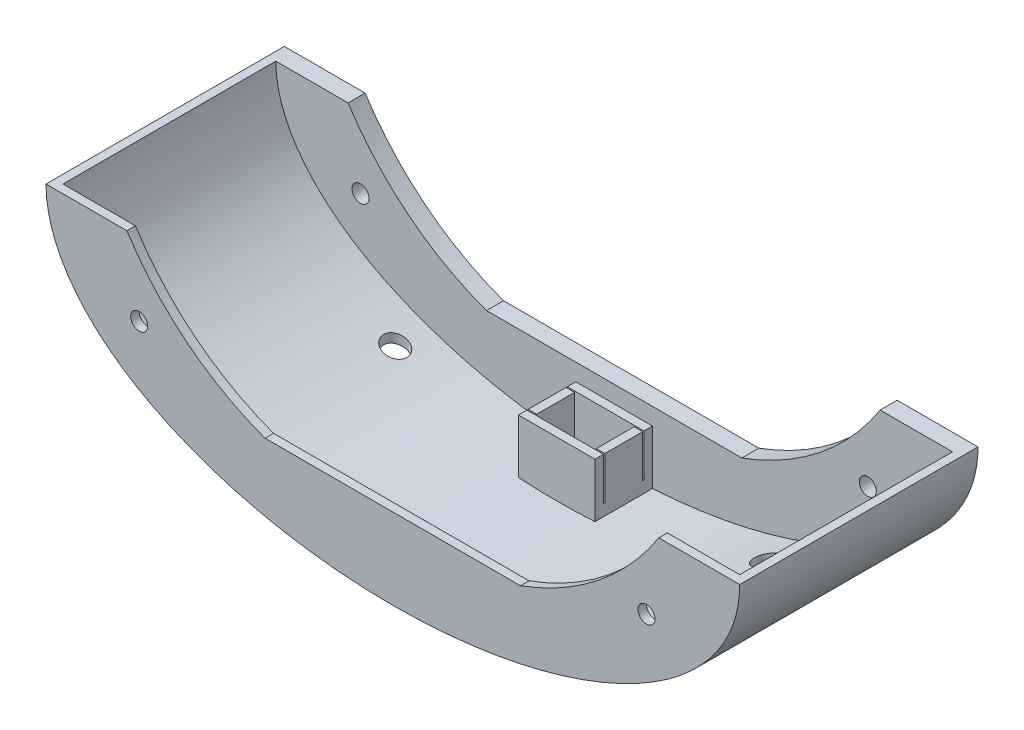
SolidWorks part; units mm, degrees
ref_plane "Alzado" through (0, 0, 0) normal (0, 0, 1) x (1, 0, 0)
ref_plane "Planta" through (0, 0, 0) normal (0, 1, 0) x (1, 0, 0)
ref_plane "Vista lateral" through (0, 0, 0) normal (1, 0, 0) x (0, 0, -1)
sketch "Croquis1" plane through (0, 0, 0) normal (0, 0, 1) x (1, 0, 0)
  line L0 (0, 14) -> (30, 14)
  line L1 (-76.5, 40) -> (-62.5, 40)
  line L2 (0, 14) -> (-30, 14)
  line L3 (0, 0) -> (0, 40) construction
  line L4 (62.5, 40) -> (76.5, 40)
  line L5 (-59.6, 23) -> (59.6, 23) construction
  line L6 (-7.25, 8) -> (7.25, 8) construction
  line L7 (81.5, 40) -> (76.5, 40)
  line L8 (-81.5, 40) -> (-76.5, 40)
  circle A1 centre (59.6, 23) radius 2
  circle A3 centre (-59.6, 23) radius 2
  arc A4 (-30, 14) -> (-62.5, 40) centre (-7.7821, 75.0849) cw
  arc A5 (30, 14) -> (62.5, 40) centre (7.7821, 75.0849) ccw
  ellipse E0 centre (0, 40) end of major axis (76.5, 40) minor radius 40 (-76.5, 40) -> (76.5, 40) ccw
  spline S0 degree 1 poles (-81.5, 40) (81.5, 40) knots 0 0 1 1 construction
  spline S1 degree 3 poles (-81.5, 40) (-81.5, 36.7505) (-80.261, 30.281) (-73.3217, 18.4428) (-57.7398, 6.4288) (-31.0655, -2.8514) (0, -6.0743) (31.0655, -2.8514) (57.7398, 6.4288) (73.3217, 18.4428) (80.261, 30.281) (81.5, 36.7505) (81.5, 40) knots 3.141593 3.141593 3.141593 3.141593 3.337942 3.534292 3.926991 4.31969 4.712389 5.105088 5.497787 5.890486 6.086836 6.283185 6.283185 6.283185 6.283185
  dimension "D3" = 65
  dimension "D4" = 4
  dimension "D1" = 153
  dimension "D2" = 30
  dimension "D5" = 40
  dimension "D6" = 14
  dimension "D7" = 14
  dimension "D8" = 119.2
  dimension "D9" = 15
  dimension "D10" = 8
  dimension "D11" = 14.5
  dimension "D12" = 5
extrude "Saliente-Extruir1" add sketch "Croquis1" along normal blind 4 contours L1 E0 L4 A5 L0 L2 A4 A1 A3 | L8 S1 L7 E0 region at (15, 12.4186, 0) region at (79, 38.309, 0)
sketch "Croquis3" plane through (0, 0, 4) normal (0, 0, 1) x (1, 0, 0)
  line L0 (-81.5, 40) -> (-79.5, 40)
  line L1 (79.5, 40) -> (81.5, 40)
  spline S1 degree 3 poles (1542.7355, -1097.7912) (170.097, 250.4745) (-119.0873, 96.5177) (-73.3217, 18.4428) (-57.7398, 6.4288) (-31.0655, -2.8514) (0, -6.0743) (31.0655, -2.8514) (57.7398, 6.4288) (73.3217, 18.4428) (119.0876, 96.5183) (-170.1018, 250.4771) (-1542.7713, -1097.8263) knots -1.252843 -1.252843 -1.252843 -1.252843 3.337942 3.534292 3.926991 4.31969 4.712389 5.105088 5.497787 5.890486 6.086836 10.67766 10.67766 10.67766 10.67766 only from (-81.5, 40) to (81.5, 40) construction
  spline S2 degree 3 poles (-81.5, 40) (-81.5, 36.7505) (-80.261, 30.281) (-73.3217, 18.4428) (-57.7398, 6.4288) (-31.0655, -2.8514) (0, -6.0743) (31.0655, -2.8514) (57.7398, 6.4288) (73.3217, 18.4428) (80.261, 30.281) (81.5, 36.7505) (81.5, 40) knots 3.141593 3.141593 3.141593 3.141593 3.337942 3.534292 3.926991 4.31969 4.712389 5.105088 5.497787 5.890486 6.086836 6.283185 6.283185 6.283185 6.283185
  spline S3 degree 1 poles (-79.5, 40) (79.5, 40) knots 0 0 1 1 construction
  spline S4 degree 3 poles (-79.5, 40) (-79.5, 36.9913) (-78.3621, 31.0317) (-73.4854, 22.677) (-65.8626, 15.2348) (-52.4779, 6.7299) (-30.655, -0.8785) (0, -4.0608) (30.655, -0.8785) (52.4779, 6.7299) (65.8626, 15.2348) (73.4854, 22.677) (78.3621, 31.0317) (79.5, 36.9913) (79.5, 40) knots 3.141593 3.141593 3.141593 3.141593 3.337942 3.534292 3.730641 3.926991 4.31969 4.712389 5.105088 5.497787 5.694137 5.890486 6.086836 6.283185 6.283185 6.283185 6.283185
  point P13 (62.5, 40)
  point P14 (64.5, 18.4921)
  point P24 (-64.9152, 40)
  point P25 (-66.5, 18.4921)
  point P26 (65.1546, 40)
  point P29 (66.5, 18.4921)
  dimension "D1" = 2
extrude "Saliente-Extruir4" add sketch "Croquis3" along normal blind 50 contours S4 S2 region at (-80.5, 38.309, 4)
sketch "Croquis4" plane through (0, 0, 4) normal (0, 0, 1) x (1, 0, 0)
  line L0 (81.5, 40) -> (79.5, 40)
  line L1 (-79.5, 40) -> (-81.5, 40)
  line L2 (62.5, 40) -> (65.1546, 40)
  line L3 (-79.5, 40) -> (-62.5, 40) construction
  line L4 (62.5, 40) -> (79.5, 40) construction
  line L6 (65.1546, 40) -> (67.1546, 40)
  line L7 (-62.5, 40) -> (-64.9152, 40)
  line L9 (-64.9152, 40) -> (-66.9152, 40)
  spline S0 degree 3 poles (2500.8694, -1422.6519) (354.3128, 300.5819) (-126.7265, 113.8887) (-73.4854, 22.677) (-65.8626, 15.2348) (-52.4779, 6.7299) (-30.655, -0.8785) (0, -4.0608) (30.655, -0.8785) (52.4779, 6.7299) (65.8626, 15.2348) (73.4854, 22.677) (126.7267, 113.889) (-354.3168, 300.5835) (-2500.8972, -1422.6743) knots -2.700246 -2.700246 -2.700246 -2.700246 3.337942 3.534292 3.730641 3.926991 4.31969 4.712389 5.105088 5.497787 5.694137 5.890486 6.086836 12.12505 12.12505 12.12505 12.12505 only from (-79.5, 40) to (79.5, 40) construction
  spline S1 degree 3 poles (-79.5, 40) (-79.5, 36.9913) (-78.3621, 31.0317) (-73.4854, 22.677) (-65.8626, 15.2348) (-52.4779, 6.7299) (-30.655, -0.8785) (0, -4.0608) (30.655, -0.8785) (52.4779, 6.7299) (65.8626, 15.2348) (73.4854, 22.677) (78.3621, 31.0317) (79.5, 36.9913) (79.5, 40) knots 3.141593 3.141593 3.141593 3.141593 3.337942 3.534292 3.730641 3.926991 4.31969 4.712389 5.105088 5.497787 5.694137 5.890486 6.086836 6.283185 6.283185 6.283185 6.283185
  spline S4 degree 3 poles (2240.2411, -1814.2164) (260.5559, 296.658) (-125.1968, 106.9403) (-73.3217, 18.4428) (-57.7398, 6.4288) (-31.0655, -2.8514) (0, -6.0743) (31.0655, -2.8514) (57.7398, 6.4288) (73.3217, 18.4428) (125.1973, 106.9411) (-260.564, 296.662) (-2240.3055, -1814.2851) knots -1.944322 -1.944322 -1.944322 -1.944322 3.337942 3.534292 3.926991 4.31969 4.712389 5.105088 5.497787 5.890486 6.086836 11.369158 11.369158 11.369158 11.369158 only from (-81.5, 40) to (81.5, 40) construction
  spline S5 degree 3 poles (-81.5, 40) (-81.5, 36.7505) (-80.261, 30.281) (-73.3217, 18.4428) (-57.7398, 6.4288) (-31.0655, -2.8514) (0, -6.0743) (31.0655, -2.8514) (57.7398, 6.4288) (73.3217, 18.4428) (80.261, 30.281) (81.5, 36.7505) (81.5, 40) knots 3.141593 3.141593 3.141593 3.141593 3.337942 3.534292 3.926991 4.31969 4.712389 5.105088 5.497787 5.890486 6.086836 6.283185 6.283185 6.283185 6.283185
extrude "Saliente-Extruir5" add sketch "Croquis4" along normal blind 50 contours S1 L0 S5 L1
ref_plane "Plano1" through (0, 40, 0) normal (0, 1, 0) x (1, 0, 0)
sketch "Croquis11" plane through (0, 0, 0) normal (0, 1, 0) x (1, 0, 0)
  line L0 (-9, -4) -> (9, -4)
  line L1 (-7, -15.5) -> (7, -15.5)
  line L2 (-7, -15.5) -> (-7, -6)
  line L3 (-7, -6) -> (7, -6)
  line L4 (7, -15.5) -> (7, -6)
  line L5 (-7, -15.5) -> (7, -6) construction
  line L6 (-7, -6) -> (7, -15.5) construction
  line L7 (9, -17.5) -> (9, -4)
  line L8 (-9, -17.5) -> (9, -17.5)
  line L9 (-9, -17.5) -> (-9, -4)
  line L10 (-9, -4) -> (9, -4)
  line L11 (-9, -4) -> (-9, -6)
  line L12 (-9, -6) -> (9, -6)
  line L13 (9, -4) -> (9, -6)
  line L14 (-9, -17.5) -> (9, -17.5)
  line L15 (-9, -17.5) -> (-9, -15.5)
  line L16 (-9, -15.5) -> (9, -15.5)
  line L17 (9, -17.5) -> (9, -15.5)
  line L18 (-9, -6.3) -> (-7, -6.3)
  line L19 (-9, -6.3) -> (-9, -15.2)
  line L20 (-9, -15.2) -> (-7, -15.2)
  line L21 (-7, -6.3) -> (-7, -15.2)
  line L22 (7, -6.3) -> (9, -6.3)
  line L23 (7, -6.3) -> (7, -15.2)
  line L24 (7, -15.2) -> (9, -15.2)
  line L25 (9, -6.3) -> (9, -15.2)
  line L28 (-30, -4) -> (30, -4) construction
  point P0 (0, -10.75)
  point P23 (0, 0)
  dimension "D1" = 9.5
  dimension "D2" = 14
  dimension "D3" = 2.3
  dimension "D4" = 2.3
  dimension "D5" = 2.3
  dimension "D6" = 2.3
  dimension "D7" = 18
  dimension "D8" = 13.5
  dimension "D9" = 0.3
  dimension "D10" = 0.3
  dimension "D11" = 2
extrude "Saliente-Extruir9" add sketch "Croquis11" along normal blind 10 contours L16 L9 L8 L7 L1 | L4 L24 L7 L22 | L9 L20 L2 L18 | L9 L12 L3 L7 L0 region at (0, 0, 5) region at (-8, 0, 10.75) region at (8, 0, 10.75) region at (0, 0, 16.5)
extrude "Saliente-Extruir10" add sketch "Croquis11<3>" against normal up to next contours L9 L20 L2 L18 | L20 L9 L16 L2 | L16 L9 L8 L7 L1 | L24 L4 L16 L7 | L4 L24 L7 L22 | L9 L12 L3 L7 L0 | L4 L22 L7 L12 | L9 L18 L2 L12 | L18 L21 L20 L19 region at (0, 0, 5) region at (-8, 0, 6.15) region at (8, 0, 6.15) region at (-8, 0, 10.75) region at (8, 0, 10.75) region at (-8, 0, 15.35) region at (8, 0, 15.35) region at (0, 0, 16.5)
sketch "Croquis11<3>" plane through (0, 0, 0) normal (0, 1, 0) x (1, 0, 0) same geometry as "Croquis11"
sketch "Croquis12" plane through (0, 10, 0) normal (0, 1, 0) x (1, 0, 0)
  line L0 (-7, -6) -> (-7, -15.5) construction
  line L1 (-7, -6) -> (7, -6) construction
  line L2 (7, -6) -> (7, -15.5) construction
  line L3 (7, -15.5) -> (-7, -15.5) construction
  line L4 (-7, -6) -> (-7, -15.5)
  line L5 (-7, -6) -> (7, -6)
  line L6 (7, -6) -> (7, -15.5)
  line L7 (7, -15.5) -> (-7, -15.5)
extrude "Cortar-Extruir4" cut sketch "Croquis12" against normal through all
sketch "Croquis13" plane through (0, 0, 54) normal (0, 0, 1) x (1, 0, 0)
  line L0 (81.5, 40) -> (79.5, 40) construction
  line L1 (62.5, 40) -> (79.5, 40) construction
  line L2 (-79.5, 40) -> (-81.5, 40) construction
  line L3 (-79.5, 40) -> (-62.5, 40) construction
  line L4 (-30, 14) -> (30, 14) construction
  line L5 (81.5, 40) -> (79.5, 40)
  line L6 (62.5, 40) -> (79.5, 40)
  line L7 (-79.5, 40) -> (-81.5, 40)
  line L8 (-79.5, 40) -> (-62.5, 40)
  line L9 (-30, 14) -> (30, 14)
  arc A0 (30, 14) -> (62.5, 40) centre (7.7821, 75.0849) ccw construction
  arc A1 (-62.5, 40) -> (-30, 14) centre (-7.7821, 75.0849) ccw construction
  arc A2 (30, 14) -> (62.5, 40) centre (7.7821, 75.0849) ccw
  arc A3 (-62.5, 40) -> (-30, 14) centre (-7.7821, 75.0849) ccw
  circle A4 centre (-59.6, 23) radius 2 construction
  circle A5 centre (59.6, 23) radius 2 construction
  circle A6 centre (-59.6, 23) radius 2
  circle A7 centre (59.6, 23) radius 2
  spline S0 degree 3 poles (2240.2411, -1814.2164) (260.5559, 296.658) (-125.1968, 106.9403) (-73.3217, 18.4428) (-57.7398, 6.4288) (-31.0655, -2.8514) (0, -6.0743) (31.0655, -2.8514) (57.7398, 6.4288) (73.3217, 18.4428) (125.1973, 106.9411) (-260.564, 296.662) (-2240.3055, -1814.2851) knots -1.944322 -1.944322 -1.944322 -1.944322 3.337942 3.534292 3.926991 4.31969 4.712389 5.105088 5.497787 5.890486 6.086836 11.369158 11.369158 11.369158 11.369158 only from (-81.5, 40) to (81.5, 40) construction
  spline S1 degree 3 poles (-81.5, 40) (-81.5, 36.7505) (-80.261, 30.281) (-73.3217, 18.4428) (-57.7398, 6.4288) (-31.0655, -2.8514) (0, -6.0743) (31.0655, -2.8514) (57.7398, 6.4288) (73.3217, 18.4428) (80.261, 30.281) (81.5, 36.7505) (81.5, 40) knots 3.141593 3.141593 3.141593 3.141593 3.337942 3.534292 3.926991 4.31969 4.712389 5.105088 5.497787 5.890486 6.086836 6.283185 6.283185 6.283185 6.283185
extrude "Saliente-Extruir11" add sketch "Croquis13" along normal blind 2
sketch "Croquis14" plane through (0, 0, 0) normal (0, 1, 0) x (1, 0, 0)
  line L0 (-43.5405, -11.8923) -> (43.5405, -11.8923) construction
  circle A0 centre (-43.5405, -11.8923) radius 2.75
  circle A1 centre (43.5405, -11.8923) radius 2.75
  point P2 (0, -11.8923)
  point P6 (-43.5405, -14.589)
  dimension "D1" = 5.5
extrude "Cortar-Extruir5" cut sketch "Croquis14" against normal through all both and the other way through all
